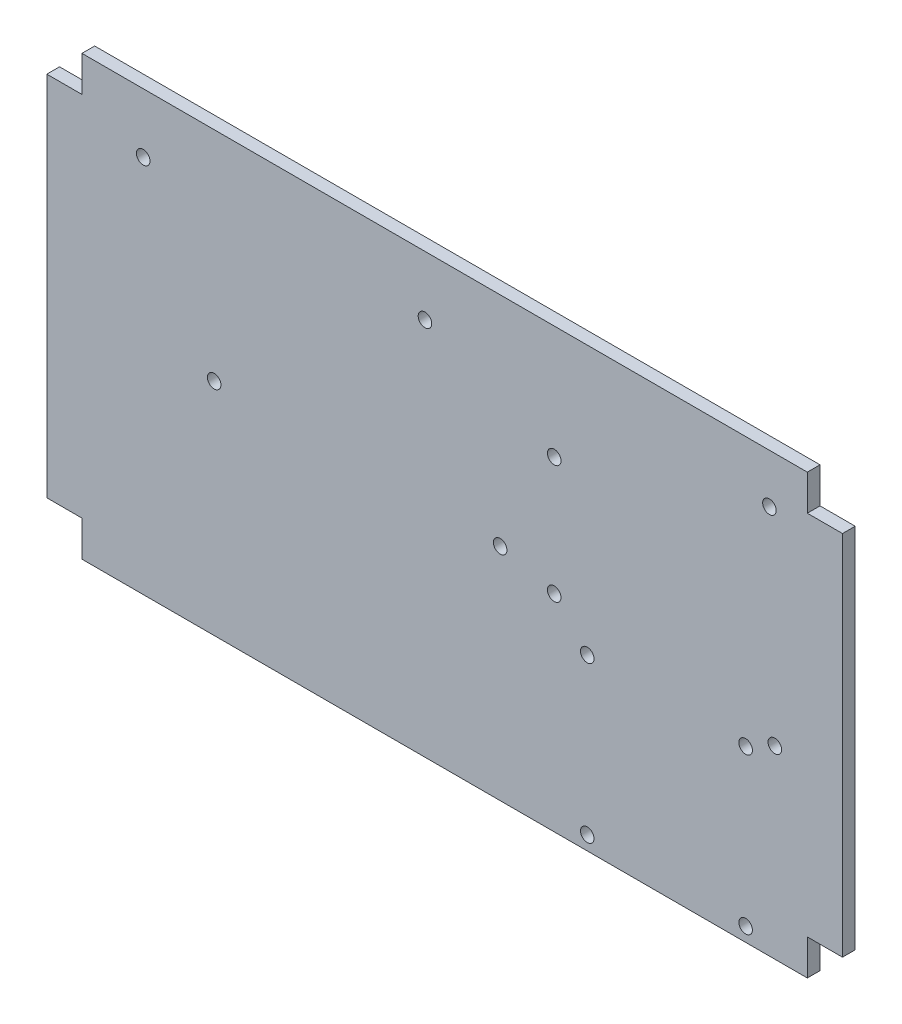
SolidWorks part; units mm, degrees
material "Сосна"
ref_plane "Спереди" through (0, 0, 0) normal (0, 0, 1) x (1, 0, 0)
ref_plane "Сверху" through (0, 0, 0) normal (0, 1, 0) x (1, 0, 0)
ref_plane "Справа" through (0, 0, 0) normal (1, 0, 0) x (0, 0, -1)
sketch "Эскиз1" plane through (0, 0, 0) normal (0, 0, 1) x (1, 0, 0)
  line L8 (93.9, -51.7) -> (93.9, 51.7)
  line L9 (93.9, 51.7) -> (-93.9, 51.7)
  line L10 (-93.9, 51.7) -> (-93.9, -51.7)
  line L11 (-93.9, -51.7) -> (93.9, -51.7)
  line L16 (93.9, -51.7) -> (93.9, 51.7)
  line L17 (93.9, 51.7) -> (-93.9, 51.7)
  line L18 (-93.9, 51.7) -> (-93.9, -51.7)
  line L19 (-93.9, -51.7) -> (93.9, -51.7)
  dimension "D1" = 0
extrude "Бобышка-Вытянуть1" add sketch "Эскиз1" along normal blind 3 contours L19 L16 L17 L18
hole_wizard "Отверстие с зазором M31" positions "Эскиз4" profile "Эскиз5" hole size "M3" standard "ISO" end condition up to next
sketch "Эскиз4" plane through (0, 0, 0) normal (0, 0, -1) x (-1, 0, 0)
  point P0 (-77.93, -8.1)
  point P3 (-25.86, -3.02)
  point P6 (-25.86, 24.92)
  point P9 (-76.66, 40.16)
  point P12 (-71.0363, -48.3857)
  point P15 (-71.0363, -11.6439)
  point P18 (-33.6568, -11.6439)
  point P21 (-33.6568, -48.3857)
  point P24 (-13.1, 0.3)
  point P27 (54.4, 0.3)
  point P38 (4.65, 37.7)
  point P41 (71.15, 37.7)
sketch "Эскиз5" plane through (77.93, -8.1, 0) normal (1, 0, 0) x (0, 1, 0)
  line L0 (0, 0) -> (0, 3)
  line L1 (0, 3) -> (1.6, 3)
  line L2 (1.6, 3) -> (1.6, 0)
  line L5 (1.6, 0) -> (0, 0)
  line L11 (0, -6.35) -> (0, 107.95) construction
  dimension "Диаметр сквозного отверстия" = 3.2
  dimension "Глубина сквозного отверстия" = 3
sketch "Эскиз6" plane through (0, 0, 0) normal (0, 0, -1) x (-1, 0, 0)
  line L0 (0, 0) -> (50000, 0) construction
  line L1 (-93.9, 51.7) -> (-85.6, 51.7)
  line L2 (-93.9, 51.7) -> (-93.9, 43.3)
  line L3 (-93.9, 43.3) -> (-85.6, 43.3)
  line L4 (-85.6, 51.7) -> (-85.6, 43.3)
  line L5 (-89.75, 43.3) -> (-89.75, 51.7) construction
  line L6 (-93.9, 47.5) -> (-85.6, 47.5) construction
  line L7 (0, 0) -> (0, -50000) construction
  line L8 (93.9, 47.5) -> (85.6, 47.5) construction
  line L9 (89.75, 43.3) -> (89.75, 51.7) construction
  line L10 (85.6, 51.7) -> (85.6, 43.3)
  line L11 (93.9, 43.3) -> (85.6, 43.3)
  line L12 (93.9, 51.7) -> (93.9, 43.3)
  line L13 (93.9, 51.7) -> (85.6, 51.7)
  line L14 (89.75, -43.3) -> (89.75, -51.7) construction
  line L15 (93.9, -47.5) -> (85.6, -47.5) construction
  line L16 (-93.9, -47.5) -> (-85.6, -47.5) construction
  line L17 (-89.75, -43.3) -> (-89.75, -51.7) construction
  line L18 (93.9, -51.7) -> (85.6, -51.7)
  line L19 (93.9, -51.7) -> (93.9, -43.3)
  line L20 (93.9, -43.3) -> (85.6, -43.3)
  line L21 (85.6, -51.7) -> (85.6, -43.3)
  line L22 (-85.6, -51.7) -> (-85.6, -43.3)
  line L23 (-93.9, -43.3) -> (-85.6, -43.3)
  line L24 (-93.9, -51.7) -> (-93.9, -43.3)
  line L25 (-93.9, -51.7) -> (-85.6, -51.7)
  point P5 (-89.75, 47.5)
  point P17 (89.75, 47.5)
  point P34 (-89.75, -47.5)
  point P35 (89.75, -47.5)
  point P68 (-89.75, 47.5)
extrude "Вырез-Вытянуть1" cut sketch "Эскиз6" against normal through all
equation "\"D1@Бобышка-Вытянуть1@G1025BF, Корпус для РЭА 225х113х63мм, пластик, черный с крепежным фланцем-1.Part\"=57.5-4"
